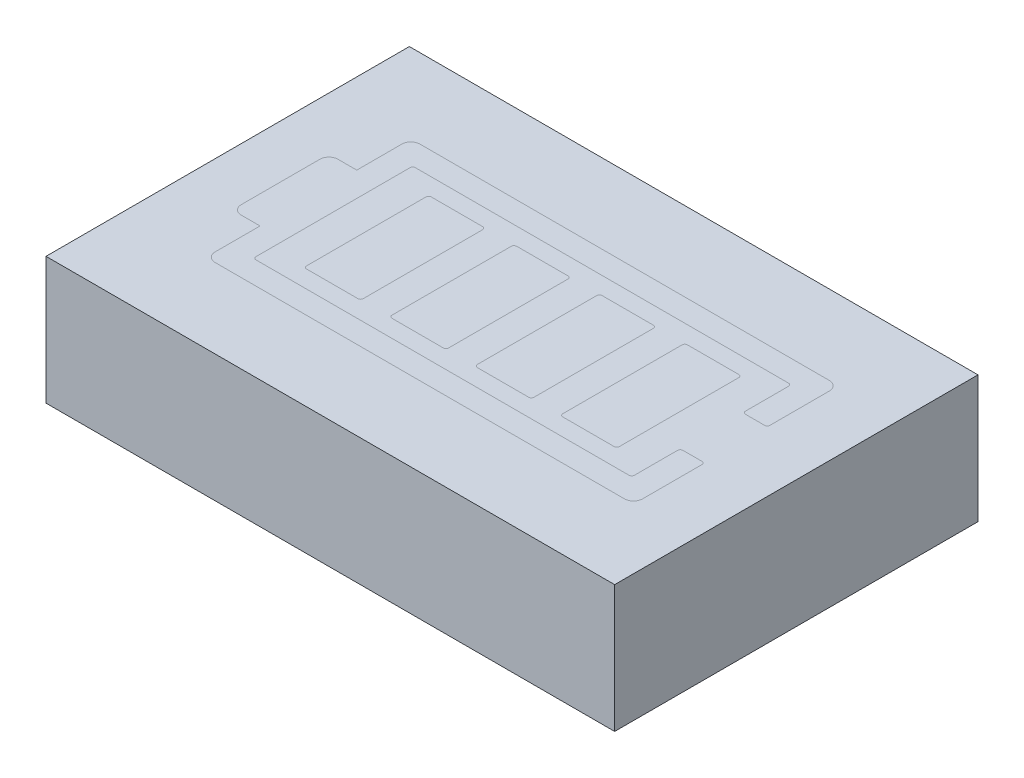
SolidWorks part; units mm, degrees
ref_plane "Front Plane" through (0, 0, 0) normal (0, 0, 1) x (1, 0, 0)
ref_plane "Top Plane" through (0, 0, 0) normal (0, 1, 0) x (1, 0, 0)
ref_plane "Right Plane" through (0, 0, 0) normal (1, 0, 0) x (0, 0, -1)
sketch "Sketch1" plane through (0, 0, 0) normal (0, 1, 0) x (1, 0, 0)
  line L0 (-14.65, -9) -> (-14.65, 9)
  line L1 (-15.65, -10) -> (15.65, -10)
  line L2 (-15.65, -10) -> (-15.65, 10)
  line L3 (-15.65, 10) -> (15.65, 10)
  line L4 (15.65, -10) -> (15.65, 10)
  line L5 (-15.65, -10) -> (15.65, 10) construction
  line L6 (-15.65, 10) -> (15.65, -10) construction
  line L7 (-14.65, 9) -> (-7, 9)
  line L8 (14.65, -9) -> (14.65, 9)
  line L9 (-14.65, -9) -> (-7, -9)
  line L10 (-7, 7) -> (-6, 7)
  line L12 (-7, 9) -> (-7, 7)
  line L14 (-6, 9) -> (-6, 7)
  line L15 (-7, 9) -> (-6.8889, 7) construction
  line L16 (-7, -9) -> (-6.8889, -7) construction
  line L17 (0, -9) -> (0, 9) construction
  line L18 (-14.65, 0) -> (14.65, 0) construction
  line L19 (-7, -7) -> (-6, -7)
  line L20 (-7, -7) -> (-7, -9)
  line L21 (-6.1111, -7) -> (-6, -9) construction
  line L22 (-6.1111, 7) -> (-6, 9) construction
  line L23 (-6, -7) -> (-6, -9)
  line L24 (-6, 9) -> (6, 9)
  line L25 (-14.65, 9) -> (14.65, 9) construction
  line L26 (-6, -9) -> (6, -9)
  line L27 (-14.65, -9) -> (14.65, -9) construction
  line L28 (6.1111, -7) -> (6, -9) construction
  line L29 (7, -9) -> (6.8889, -7) construction
  line L30 (6, -7) -> (6, -9)
  line L31 (7, -7) -> (7, -9)
  line L32 (7, -7) -> (6, -7)
  line L33 (6.1111, 7) -> (6, 9) construction
  line L34 (7, 9) -> (6.8889, 7) construction
  line L35 (6, 9) -> (6, 7)
  line L36 (7, 9) -> (7, 7)
  line L37 (7, 7) -> (6, 7)
  line L38 (7, 9) -> (14.65, 9)
  line L39 (7, -9) -> (14.65, -9)
  point P0 (0, 0)
  point P14 (-6.5, 0)
  point P20 (0, 0)
  point P23 (0, 0)
  dimension "D1" = 20
  dimension "D2" = 31.3
  dimension "D4" = 1
  dimension "D5" = 6
  dimension "D6" = 2
  dimension "D3" = 1
extrude "Boss-Extrude1" add sketch "Sketch1" along normal blind 7
sketch "Sketch2" plane through (0, 7, 0) normal (0, 1, 0) x (1, 0, 0)
  line L0 (15.65, -10) -> (15.65, 10) construction
  line L1 (-15.65, -10) -> (15.65, -10) construction
  line L2 (-15.65, 10) -> (-15.65, -10) construction
  line L3 (15.65, 10) -> (-15.65, 10) construction
  line L4 (15.65, -10) -> (15.65, 10)
  line L5 (-15.65, -10) -> (15.65, -10)
  line L6 (-15.65, 10) -> (-15.65, -10)
  line L7 (15.65, 10) -> (-15.65, 10)
extrude "Boss-Extrude2" add sketch "Sketch2" against normal blind 1
sketch "Sketch3" plane through (0, 0, 0) normal (0, -1, 0) x (1, 0, 0)
  line L0 (-14.65, -9) -> (-14.65, 9) construction
  line L1 (-14.65, -9) -> (-14.65, 9)
  line L2 (14.65, 9) -> (14.65, -9) construction
  line L3 (14.65, 9) -> (14.65, -9)
  line L4 (-14.65, 9) -> (14.65, 9)
  line L5 (-14.65, -9) -> (14.65, -9)
extrude "Boss-Extrude4" add sketch "Sketch3" against normal up to surface (6 mm away) from offset 0.25 up to face at (0, 6, 0) offset against normal yes
sketch "Sketch4" plane through (0, 7, 0) normal (0, 1, 0) x (1, 0, 0)
  line L0 (15.65, 0) -> (-4.9013, 0) construction
  line L1 (15.65, -10) -> (15.65, 10) construction
  line L2 (-15.65, 10) -> (-15.65, -10) construction
  line L3 (-9.8559, 4.2413) -> (-9.8559, -4.2413)
  line L4 (-9.7059, 4.3913) -> (10.8308, 4.3913)
  line L5 (10.9808, 4.2413) -> (10.9808, 1.8698)
  line L6 (11.1308, 1.7198) -> (12.1808, 1.7198)
  line L7 (12.3308, 1.8698) -> (12.3308, 5.1413)
  line L8 (11.8308, 5.6413) -> (-10.7059, 5.6413)
  line L9 (-11.2059, 5.1413) -> (-11.2059, 2.6617)
  line L10 (-11.2059, 2.6617) -> (-12.24, 2.6617)
  line L11 (-12.74, 2.1617) -> (-12.74, -2.1617)
  line L12 (-11.2059, -2.6617) -> (-12.24, -2.6617)
  line L13 (-11.2059, -5.1413) -> (-11.2059, -2.6617)
  line L14 (11.8308, -5.6413) -> (-10.7059, -5.6413)
  line L15 (12.3308, -1.8698) -> (12.3308, -5.1413)
  line L16 (11.1308, -1.7198) -> (12.1808, -1.7198)
  line L17 (10.9808, -4.2413) -> (10.9808, -1.8698)
  line L18 (-9.7059, -4.3913) -> (10.8308, -4.3913)
  line L19 (-8.0236, 0) -> (-15.65, 0) construction
  line L20 (-7.8736, 3.4332) -> (-5.0513, 3.4332)
  line L21 (-8.0236, 3.2832) -> (-8.0236, -3.2832)
  line L23 (-4.9013, 3.2832) -> (-4.9013, -3.2832)
  line L24 (-8.0236, 3.4332) -> (-4.9013, 0) construction
  line L25 (-8.0236, 0) -> (-4.9013, 3.4332) construction
  line L26 (-0.2013, 3.2832) -> (-0.2013, -3.2832)
  line L27 (-3.3236, 0) -> (-0.2013, 3.4332) construction
  line L28 (-3.3236, 3.4332) -> (-0.2013, 0) construction
  line L29 (-3.3236, 3.2832) -> (-3.3236, -3.2832)
  line L30 (-3.1736, 3.4332) -> (-0.3513, 3.4332)
  line L31 (4.4987, 3.2832) -> (4.4987, -3.2832)
  line L32 (1.3764, 0) -> (4.4987, 3.4332) construction
  line L33 (1.3764, 3.4332) -> (4.4987, 0) construction
  line L34 (1.3764, 3.2832) -> (1.3764, -3.2832)
  line L35 (1.5264, 3.4332) -> (4.3487, 3.4332)
  line L36 (9.1987, 3.2832) -> (9.1987, -3.2832)
  line L37 (6.0764, 0) -> (9.1987, 3.4332) construction
  line L38 (6.0764, 3.4332) -> (9.1987, 0) construction
  line L39 (6.0764, 3.2832) -> (6.0764, -3.2832)
  line L40 (6.2264, 3.4332) -> (9.0487, 3.4332)
  line L41 (6.0764, -3.4332) -> (9.1987, 0) construction
  line L42 (6.0764, 0) -> (9.1987, -3.4332) construction
  line L43 (1.3764, -3.4332) -> (4.4987, 0) construction
  line L44 (1.3764, 0) -> (4.4987, -3.4332) construction
  line L45 (-3.3236, -3.4332) -> (-0.2013, 0) construction
  line L46 (-3.3236, 0) -> (-0.2013, -3.4332) construction
  line L47 (-8.0236, 0) -> (-4.9013, -3.4332) construction
  line L48 (-8.0236, -3.4332) -> (-4.9013, 0) construction
  line L49 (6.2264, -3.4332) -> (9.0487, -3.4332)
  line L50 (1.5264, -3.4332) -> (4.3487, -3.4332)
  line L51 (-3.1736, -3.4332) -> (-0.3513, -3.4332)
  line L52 (-7.8736, -3.4332) -> (-5.0513, -3.4332)
  arc A0 (10.8308, 4.3913) -> (10.9808, 4.2413) centre (10.8308, 4.2413) cw
  arc A1 (-9.8559, 4.2413) -> (-9.7059, 4.3913) centre (-9.7059, 4.2413) cw
  arc A2 (-12.24, 2.6617) -> (-12.74, 2.1617) centre (-12.24, 2.1617) ccw
  arc A3 (12.3308, 5.1413) -> (11.8308, 5.6413) centre (11.8308, 5.1413) ccw
  arc A4 (-10.7059, 5.6413) -> (-11.2059, 5.1413) centre (-10.7059, 5.1413) ccw
  arc A5 (12.1808, 1.7198) -> (12.3308, 1.8698) centre (12.1808, 1.8698) ccw
  arc A6 (10.9808, 1.8698) -> (11.1308, 1.7198) centre (11.1308, 1.8698) ccw
  arc A7 (10.9808, -1.8698) -> (11.1308, -1.7198) centre (11.1308, -1.8698) cw
  arc A8 (12.1808, -1.7198) -> (12.3308, -1.8698) centre (12.1808, -1.8698) cw
  arc A9 (-10.7059, -5.6413) -> (-11.2059, -5.1413) centre (-10.7059, -5.1413) cw
  arc A10 (12.3308, -5.1413) -> (11.8308, -5.6413) centre (11.8308, -5.1413) cw
  arc A11 (-12.24, -2.6617) -> (-12.74, -2.1617) centre (-12.24, -2.1617) cw
  arc A12 (-9.8559, -4.2413) -> (-9.7059, -4.3913) centre (-9.7059, -4.2413) ccw
  arc A13 (10.8308, -4.3913) -> (10.9808, -4.2413) centre (10.8308, -4.2413) ccw
  arc A14 (-5.0513, 3.4332) -> (-4.9013, 3.2832) centre (-5.0513, 3.2832) cw
  arc A15 (-7.8736, 3.4332) -> (-8.0236, 3.2832) centre (-7.8736, 3.2832) ccw
  arc A16 (-0.3513, 3.4332) -> (-0.2013, 3.2832) centre (-0.3513, 3.2832) cw
  arc A17 (-3.1736, 3.4332) -> (-3.3236, 3.2832) centre (-3.1736, 3.2832) ccw
  arc A18 (4.3487, 3.4332) -> (4.4987, 3.2832) centre (4.3487, 3.2832) cw
  arc A19 (1.5264, 3.4332) -> (1.3764, 3.2832) centre (1.5264, 3.2832) ccw
  arc A20 (9.0487, 3.4332) -> (9.1987, 3.2832) centre (9.0487, 3.2832) cw
  arc A21 (6.2264, 3.4332) -> (6.0764, 3.2832) centre (6.2264, 3.2832) ccw
  arc A22 (6.2264, -3.4332) -> (6.0764, -3.2832) centre (6.2264, -3.2832) cw
  arc A23 (9.0487, -3.4332) -> (9.1987, -3.2832) centre (9.0487, -3.2832) ccw
  arc A24 (1.5264, -3.4332) -> (1.3764, -3.2832) centre (1.5264, -3.2832) cw
  arc A25 (4.3487, -3.4332) -> (4.4987, -3.2832) centre (4.3487, -3.2832) ccw
  arc A26 (-3.1736, -3.4332) -> (-3.3236, -3.2832) centre (-3.1736, -3.2832) cw
  arc A27 (-0.3513, -3.4332) -> (-0.2013, -3.2832) centre (-0.3513, -3.2832) ccw
  arc A28 (-7.8736, -3.4332) -> (-8.0236, -3.2832) centre (-7.8736, -3.2832) cw
  arc A29 (-5.0513, -3.4332) -> (-4.9013, -3.2832) centre (-5.0513, -3.2832) ccw
  point P9 (-9.8559, 0)
  point P52 (-12.74, 0)
  point P53 (-9.8559, 0)
  point P57 (-6.4624, 1.7166)
  point P126 (-6.4624, -1.7166)
  dimension "D4" = 0.15
  dimension "D5" = 0.5
  dimension "D6" = 0.15
  dimension "D7" = 0.15
  dimension "D1" = 1.35
  dimension "D2" = 1.25
  dimension "D3" = 1.35
  dimension "D8" = 4
ref_plane "Plane1" through (0, 17, 0) normal (0, 1, 0) x (1, 0, 0)
sketch "Sketch5" plane through (0, 17, 0) normal (0, 1, 0) x (1, 0, 0)
  line L0 (1.5264, -3.4332) -> (4.3487, -3.4332) construction
  line L1 (4.4987, 3.2832) -> (4.4987, -3.2832) construction
  line L2 (1.3764, 3.2832) -> (1.3764, -3.2832) construction
  line L3 (1.5264, 3.4332) -> (4.3487, 3.4332) construction
  line L4 (-3.1736, -3.4332) -> (-0.3513, -3.4332) construction
  line L5 (-0.2013, 3.2832) -> (-0.2013, -3.2832) construction
  line L6 (-3.3236, 3.2832) -> (-3.3236, -3.2832) construction
  line L7 (-3.1736, 3.4332) -> (-0.3513, 3.4332) construction
  line L8 (6.2264, -3.4332) -> (9.0487, -3.4332) construction
  line L9 (6.0764, 3.2832) -> (6.0764, -3.2832) construction
  line L10 (9.1987, 3.2832) -> (9.1987, -3.2832) construction
  line L11 (6.2264, 3.4332) -> (9.0487, 3.4332) construction
  line L12 (12.3308, -1.8698) -> (12.3308, -5.1413) construction
  line L13 (11.1308, -1.7198) -> (12.1808, -1.7198) construction
  line L14 (10.9808, -4.2413) -> (10.9808, -1.8698) construction
  line L15 (11.1308, 1.7198) -> (12.1808, 1.7198) construction
  line L16 (10.9808, 4.2413) -> (10.9808, 1.8698) construction
  line L17 (12.3308, 1.8698) -> (12.3308, 5.1413) construction
  line L18 (-4.9013, 3.2832) -> (-4.9013, -3.2832) construction
  line L19 (-7.8736, -3.4332) -> (-5.0513, -3.4332) construction
  line L20 (-9.7059, -4.3913) -> (10.8308, -4.3913) construction
  line L21 (11.8308, -5.6413) -> (-10.7059, -5.6413) construction
  line L22 (-11.2059, -5.1413) -> (-11.2059, -2.6617) construction
  line L23 (-11.2059, -2.6617) -> (-12.24, -2.6617) construction
  line L24 (-8.0236, 3.2832) -> (-8.0236, -3.2832) construction
  line L25 (-7.8736, 3.4332) -> (-5.0513, 3.4332) construction
  line L26 (-9.7059, 4.3913) -> (10.8308, 4.3913) construction
  line L27 (-9.8559, 4.2413) -> (-9.8559, -4.2413) construction
  line L28 (-12.74, 2.1617) -> (-12.74, -2.1617) construction
  line L29 (-11.2059, 2.6617) -> (-12.24, 2.6617) construction
  line L30 (-11.2059, 5.1413) -> (-11.2059, 2.6617) construction
  line L31 (11.8308, 5.6413) -> (-10.7059, 5.6413) construction
  line L32 (1.5264, -3.4332) -> (4.3487, -3.4332)
  line L33 (4.4987, 3.2832) -> (4.4987, -3.2832)
  line L34 (1.3764, 3.2832) -> (1.3764, -3.2832)
  line L35 (1.5264, 3.4332) -> (4.3487, 3.4332)
  line L36 (-3.1736, -3.4332) -> (-0.3513, -3.4332)
  line L37 (-0.2013, 3.2832) -> (-0.2013, -3.2832)
  line L38 (-3.3236, 3.2832) -> (-3.3236, -3.2832)
  line L39 (-3.1736, 3.4332) -> (-0.3513, 3.4332)
  line L40 (6.2264, -3.4332) -> (9.0487, -3.4332)
  line L41 (6.0764, 3.2832) -> (6.0764, -3.2832)
  line L42 (9.1987, 3.2832) -> (9.1987, -3.2832)
  line L43 (6.2264, 3.4332) -> (9.0487, 3.4332)
  line L44 (12.3308, -1.8698) -> (12.3308, -5.1413)
  line L45 (11.1308, -1.7198) -> (12.1808, -1.7198)
  line L46 (10.9808, -4.2413) -> (10.9808, -1.8698)
  line L47 (11.1308, 1.7198) -> (12.1808, 1.7198)
  line L48 (10.9808, 4.2413) -> (10.9808, 1.8698)
  line L49 (12.3308, 1.8698) -> (12.3308, 5.1413)
  line L50 (-4.9013, 3.2832) -> (-4.9013, -3.2832)
  line L51 (-7.8736, -3.4332) -> (-5.0513, -3.4332)
  line L52 (-9.7059, -4.3913) -> (10.8308, -4.3913)
  line L53 (11.8308, -5.6413) -> (-10.7059, -5.6413)
  line L54 (-11.2059, -5.1413) -> (-11.2059, -2.6617)
  line L55 (-11.2059, -2.6617) -> (-12.24, -2.6617)
  line L56 (-8.0236, 3.2832) -> (-8.0236, -3.2832)
  line L57 (-7.8736, 3.4332) -> (-5.0513, 3.4332)
  line L58 (-9.7059, 4.3913) -> (10.8308, 4.3913)
  line L59 (-9.8559, 4.2413) -> (-9.8559, -4.2413)
  line L60 (-12.74, 2.1617) -> (-12.74, -2.1617)
  line L61 (-11.2059, 2.6617) -> (-12.24, 2.6617)
  line L62 (-11.2059, 5.1413) -> (-11.2059, 2.6617)
  line L63 (11.8308, 5.6413) -> (-10.7059, 5.6413)
  arc A0 (4.3487, -3.4332) -> (4.4987, -3.2832) centre (4.3487, -3.2832) ccw construction
  arc A1 (1.3764, -3.2832) -> (1.5264, -3.4332) centre (1.5264, -3.2832) ccw construction
  arc A2 (4.4987, 3.2832) -> (4.3487, 3.4332) centre (4.3487, 3.2832) ccw construction
  arc A3 (1.5264, 3.4332) -> (1.3764, 3.2832) centre (1.5264, 3.2832) ccw construction
  arc A4 (-0.3513, -3.4332) -> (-0.2013, -3.2832) centre (-0.3513, -3.2832) ccw construction
  arc A5 (-3.3236, -3.2832) -> (-3.1736, -3.4332) centre (-3.1736, -3.2832) ccw construction
  arc A6 (-3.1736, 3.4332) -> (-3.3236, 3.2832) centre (-3.1736, 3.2832) ccw construction
  arc A7 (-0.2013, 3.2832) -> (-0.3513, 3.4332) centre (-0.3513, 3.2832) ccw construction
  arc A8 (9.0487, -3.4332) -> (9.1987, -3.2832) centre (9.0487, -3.2832) ccw construction
  arc A9 (6.0764, -3.2832) -> (6.2264, -3.4332) centre (6.2264, -3.2832) ccw construction
  arc A10 (6.2264, 3.4332) -> (6.0764, 3.2832) centre (6.2264, 3.2832) ccw construction
  arc A11 (9.1987, 3.2832) -> (9.0487, 3.4332) centre (9.0487, 3.2832) ccw construction
  arc A12 (11.8308, -5.6413) -> (12.3308, -5.1413) centre (11.8308, -5.1413) ccw construction
  arc A13 (12.3308, -1.8698) -> (12.1808, -1.7198) centre (12.1808, -1.8698) ccw construction
  arc A14 (11.1308, -1.7198) -> (10.9808, -1.8698) centre (11.1308, -1.8698) ccw construction
  arc A15 (10.8308, -4.3913) -> (10.9808, -4.2413) centre (10.8308, -4.2413) ccw construction
  arc A16 (12.1808, 1.7198) -> (12.3308, 1.8698) centre (12.1808, 1.8698) ccw construction
  arc A17 (10.9808, 1.8698) -> (11.1308, 1.7198) centre (11.1308, 1.8698) ccw construction
  arc A18 (12.3308, 5.1413) -> (11.8308, 5.6413) centre (11.8308, 5.1413) ccw construction
  arc A19 (10.9808, 4.2413) -> (10.8308, 4.3913) centre (10.8308, 4.2413) ccw construction
  arc A20 (-5.0513, -3.4332) -> (-4.9013, -3.2832) centre (-5.0513, -3.2832) ccw construction
  arc A21 (-4.9013, 3.2832) -> (-5.0513, 3.4332) centre (-5.0513, 3.2832) ccw construction
  arc A22 (-8.0236, -3.2832) -> (-7.8736, -3.4332) centre (-7.8736, -3.2832) ccw construction
  arc A23 (-11.2059, -5.1413) -> (-10.7059, -5.6413) centre (-10.7059, -5.1413) ccw construction
  arc A24 (-9.8559, -4.2413) -> (-9.7059, -4.3913) centre (-9.7059, -4.2413) ccw construction
  arc A25 (-12.74, -2.1617) -> (-12.24, -2.6617) centre (-12.24, -2.1617) ccw construction
  arc A26 (-7.8736, 3.4332) -> (-8.0236, 3.2832) centre (-7.8736, 3.2832) ccw construction
  arc A27 (-9.7059, 4.3913) -> (-9.8559, 4.2413) centre (-9.7059, 4.2413) ccw construction
  arc A28 (-12.24, 2.6617) -> (-12.74, 2.1617) centre (-12.24, 2.1617) ccw construction
  arc A29 (-10.7059, 5.6413) -> (-11.2059, 5.1413) centre (-10.7059, 5.1413) ccw construction
  arc A30 (4.3487, -3.4332) -> (4.4987, -3.2832) centre (4.3487, -3.2832) ccw
  arc A31 (1.3764, -3.2832) -> (1.5264, -3.4332) centre (1.5264, -3.2832) ccw
  arc A32 (4.4987, 3.2832) -> (4.3487, 3.4332) centre (4.3487, 3.2832) ccw
  arc A33 (1.5264, 3.4332) -> (1.3764, 3.2832) centre (1.5264, 3.2832) ccw
  arc A34 (-0.3513, -3.4332) -> (-0.2013, -3.2832) centre (-0.3513, -3.2832) ccw
  arc A35 (-3.3236, -3.2832) -> (-3.1736, -3.4332) centre (-3.1736, -3.2832) ccw
  arc A36 (-3.1736, 3.4332) -> (-3.3236, 3.2832) centre (-3.1736, 3.2832) ccw
  arc A37 (-0.2013, 3.2832) -> (-0.3513, 3.4332) centre (-0.3513, 3.2832) ccw
  arc A38 (9.0487, -3.4332) -> (9.1987, -3.2832) centre (9.0487, -3.2832) ccw
  arc A39 (6.0764, -3.2832) -> (6.2264, -3.4332) centre (6.2264, -3.2832) ccw
  arc A40 (6.2264, 3.4332) -> (6.0764, 3.2832) centre (6.2264, 3.2832) ccw
  arc A41 (9.1987, 3.2832) -> (9.0487, 3.4332) centre (9.0487, 3.2832) ccw
  arc A42 (11.8308, -5.6413) -> (12.3308, -5.1413) centre (11.8308, -5.1413) ccw
  arc A43 (12.3308, -1.8698) -> (12.1808, -1.7198) centre (12.1808, -1.8698) ccw
  arc A44 (11.1308, -1.7198) -> (10.9808, -1.8698) centre (11.1308, -1.8698) ccw
  arc A45 (10.8308, -4.3913) -> (10.9808, -4.2413) centre (10.8308, -4.2413) ccw
  arc A46 (12.1808, 1.7198) -> (12.3308, 1.8698) centre (12.1808, 1.8698) ccw
  arc A47 (10.9808, 1.8698) -> (11.1308, 1.7198) centre (11.1308, 1.8698) ccw
  arc A48 (12.3308, 5.1413) -> (11.8308, 5.6413) centre (11.8308, 5.1413) ccw
  arc A49 (10.9808, 4.2413) -> (10.8308, 4.3913) centre (10.8308, 4.2413) ccw
  arc A50 (-5.0513, -3.4332) -> (-4.9013, -3.2832) centre (-5.0513, -3.2832) ccw
  arc A51 (-4.9013, 3.2832) -> (-5.0513, 3.4332) centre (-5.0513, 3.2832) ccw
  arc A52 (-8.0236, -3.2832) -> (-7.8736, -3.4332) centre (-7.8736, -3.2832) ccw
  arc A53 (-11.2059, -5.1413) -> (-10.7059, -5.6413) centre (-10.7059, -5.1413) ccw
  arc A54 (-9.8559, -4.2413) -> (-9.7059, -4.3913) centre (-9.7059, -4.2413) ccw
  arc A55 (-12.74, -2.1617) -> (-12.24, -2.6617) centre (-12.24, -2.1617) ccw
  arc A56 (-7.8736, 3.4332) -> (-8.0236, 3.2832) centre (-7.8736, 3.2832) ccw
  arc A57 (-9.7059, 4.3913) -> (-9.8559, 4.2413) centre (-9.7059, 4.2413) ccw
  arc A58 (-12.24, 2.6617) -> (-12.74, 2.1617) centre (-12.24, 2.1617) ccw
  arc A59 (-10.7059, 5.6413) -> (-11.2059, 5.1413) centre (-10.7059, 5.1413) ccw
split line "Split Line1"
